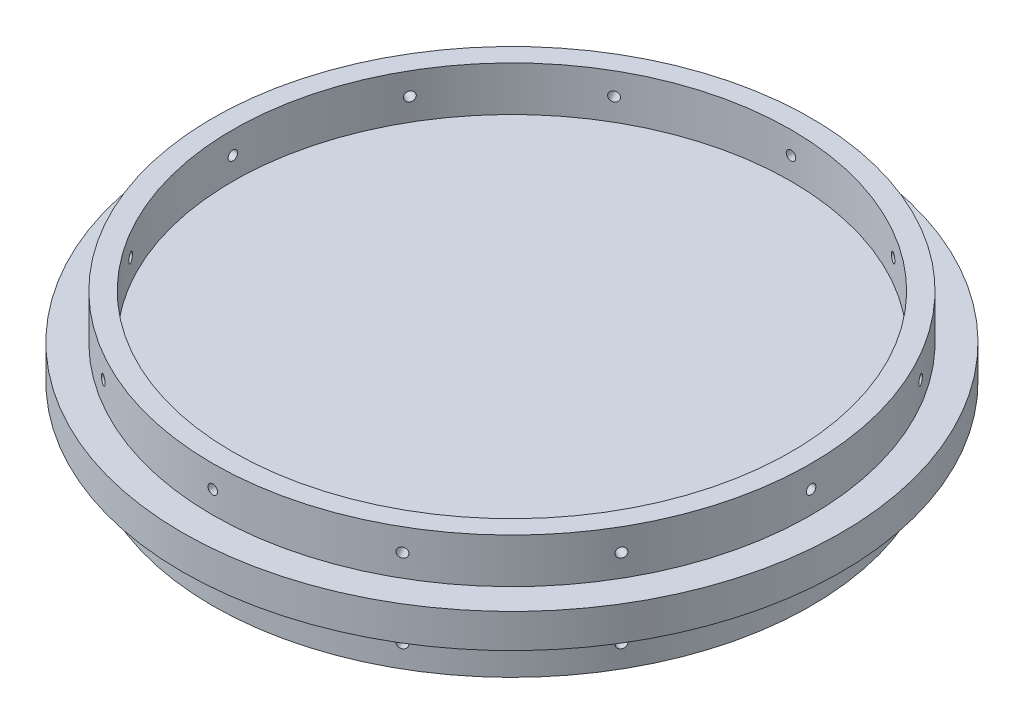
SolidWorks part; units mm, degrees
material "6061-T6 (SS)"
ref_plane "Front Plane" through (0, 0, 0) normal (0, 0, 1) x (1, 0, 0)
ref_plane "Top Plane" through (0, 0, 0) normal (0, 1, 0) x (1, 0, 0)
ref_plane "Right Plane" through (0, 0, 0) normal (1, 0, 0) x (0, 0, -1)
sketch "Sketch1" plane through (0, 0, 0) normal (0, 1, 0) x (1, 0, 0)
  circle A0 centre (0, 0) radius 93.726
  dimension "D1" = 187.452
extrude "Boss-Extrude1" add sketch "Sketch1" along normal mid plane 9.652
sketch "Sketch2" plane through (0, 0, 0) normal (0, 0, 1) x (1, 0, 0)
  line L0 (0, -18.3275) -> (0, 20.8308) construction
  line L1 (0, -4.826) -> (-25.4, -4.826)
  line L2 (-93.726, -4.826) -> (93.726, -4.826) construction
  line L3 (0, -4.826) -> (0, 1.27)
  spline S0 degree 3 poles (0, 1.27) (-5.1197, 1.5129) (-13.6852, -0.4966) (-22.1585, -2.9398) (-25.4, -4.826) knots 0 0 0 0 0.575799 1 1 1 1
  point P7 (-14.5845, 3.7084)
  point P8 (-6.214, 5.6242)
  point P11 (-14.374, 2.0678)
  point P12 (0, 2.102)
  point P14 (-6.5495, 1.9416)
  point P16 (-14.7672, 0.211)
  point P17 (-6.9019, 0.848)
  point P18 (-14.9531, -0.945)
  point P19 (-22.1564, -3.2368)
  dimension "D1" = 25.4
  dimension "D2" = 6.096
revolve "Cut-Revolve1" cut sketch "Sketch2" angle 360 about L0
sketch "Sketch4" plane through (0, 4.826, 0) normal (0, 1, 0) x (1, 0, 0)
  circle A0 centre (0, 0) radius 85.09
  circle A1 centre (0, 0) radius 79.375
  dimension "D1" = 170.18
  dimension "D2" = 158.75
extrude "Boss-Extrude2" add sketch "Sketch4" along normal blind 12.7
ref_plane "Plane1" through (0, 0, -85.09) normal (0, 0, -1) x (-1, 0, 0)
sketch "Sketch5" plane through (0, 0, -85.09) normal (0, 0, -1) x (-1, 0, 0)
  line L0 (0, 19.2786) -> (0, -19.2786) construction
  line L1 (79.375, 17.526) -> (-79.375, 17.526) construction
  circle A0 centre (0, 11.176) radius 1.3525
  dimension "D1" = 2.7051
  dimension "D2" = 6.35
extrude "Cut-Extrude2" cut sketch "Sketch5" against normal blind 12.7
pattern_circular "CirPattern1" count 12 over 360 about axis through (0, 17.526, 0) along (0, -1, 0) of "Cut-Extrude2" reverse direction yes
mirror "Mirror2" about plane through (0, 0, 0) normal (0, 1, 0) of "CirPattern1", "Cut-Extrude2", "Boss-Extrude2"
sketch "Sketch6" plane through (0, 4.826, 0) normal (0, 1, 0) x (1, 0, 0)
  line L0 (-63.5, 0) -> (-69.85, 0)
  line L1 (0, -69.85) -> (0, -63.5)
  line L2 (0, -19.2786) -> (0, 19.2786) construction
  arc A0 (-69.85, 0) -> (0, -69.85) centre (0, 0) ccw
  arc A1 (-63.5, 0) -> (0, -63.5) centre (0, 0) ccw
  dimension "D1" = 69.85
  dimension "D2" = 63.5
  dimension "D3" = 90
extrude "Cut-Extrude3" [suppressed] cut sketch "Sketch6" against normal up to surface (9.652 mm away) up to face at (0, -4.826, -25.4)
